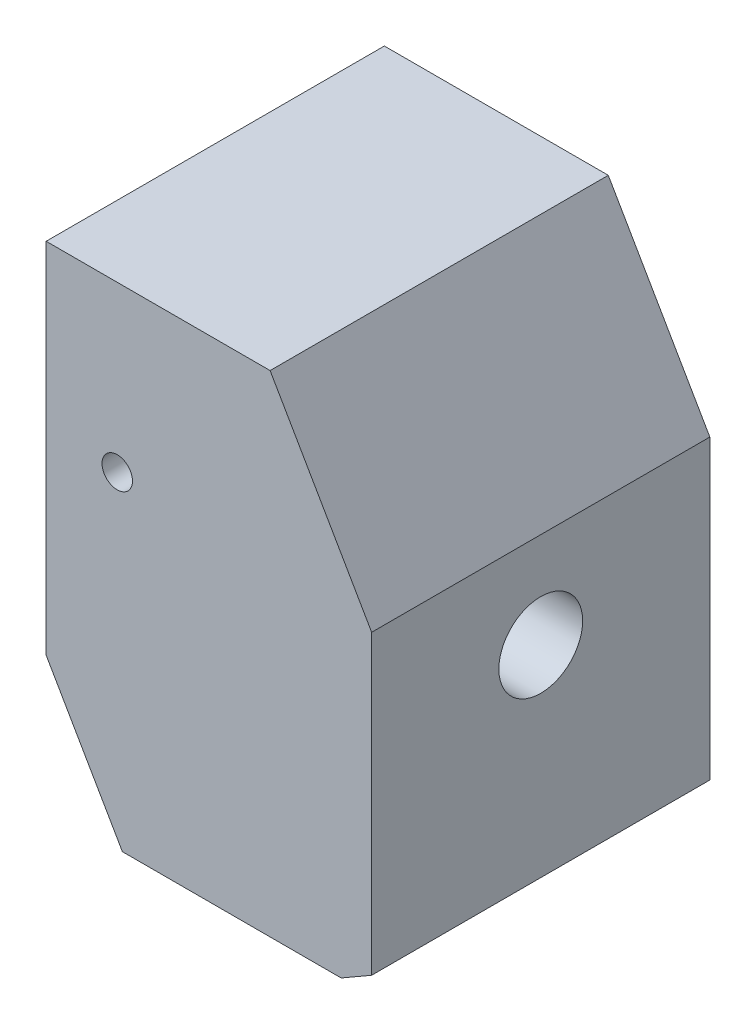
SolidWorks part; units mm, degrees
ref_plane "Front Plane" through (0, 0, 0) normal (0, 0, 1) x (1, 0, 0)
ref_plane "Top Plane" through (0, 0, 0) normal (0, 1, 0) x (1, 0, 0)
ref_plane "Right Plane" through (0, 0, 0) normal (1, 0, 0) x (0, 0, -1)
sketch "Sketch1" plane through (0, 0, 0) normal (1, 0, 0) x (0, 0, -1)
  line L1 (-16.65, 24.15) -> (16.65, 24.15)
  line L2 (-16.65, 24.15) -> (-16.65, -24.15)
  line L3 (-16.65, -24.15) -> (16.65, -24.15)
  line L4 (16.65, 24.15) -> (16.65, -24.15)
  line L5 (-16.65, 24.15) -> (16.65, -24.15) construction
  line L6 (-16.65, -24.15) -> (16.65, 24.15) construction
  point P0 (0, 0)
  dimension "D1" = 48.3
  dimension "D2" = 33.3
extrude "Boss-Extrude1" add sketch "Sketch1" along normal blind 9.55
sketch "Sketch2" plane through (0, 0, 0) normal (-1, 0, 0) x (0, 0, 1)
  line L0 (0, 24.15) -> (0, 19.15) construction
  line L3 (-16.65, 24.15) -> (16.65, 24.15) construction
  line L4 (0, 19.15) -> (0, -19.451) construction
  line L5 (0, -19.451) -> (0, -24.15) construction
  line L6 (16.65, -24.15) -> (-16.65, -24.15) construction
  line L7 (0, 19.15) -> (-5.65, 19.15)
  line L8 (-5.65, 19.15) -> (-5.65, 5.45)
  line L9 (-5.65, 5.45) -> (-11.65, -0.9874)
  line L10 (-11.65, -0.9874) -> (-11.65, -9.1)
  line L11 (-11.65, -9.1) -> (-10.5771, -10.1)
  line L12 (-10.5771, -10.1) -> (10.5771, -10.1)
  line L13 (11.65, -9.1) -> (10.5771, -10.1)
  line L14 (11.65, -0.9874) -> (11.65, -9.1)
  line L15 (5.65, 5.45) -> (11.65, -0.9874)
  line L16 (5.65, 5.45) -> (5.65, 11.45)
  line L17 (5.65, 11.45) -> (4.5, 12.6)
  line L18 (4.5, 12.6) -> (4.5, 19.15)
  line L19 (4.5, 19.15) -> (0, 19.15)
  point P16 (0, -10.1)
  dimension "D1" = 5
  dimension "D2" = 4.699
  dimension "D3" = 11.65
  dimension "D4" = 15.55
  dimension "D5" = 5.65
  dimension "D6" = 13.7
  dimension "D7" = 8.8
  dimension "D8" = 1
  dimension "D9" = 6
  dimension "D10" = 7.15
  dimension "D11" = 4.5
extrude "Cut-Extrude1" cut sketch "Sketch2" against normal blind 5
sketch "Sketch3" plane through (5, 0, 0) normal (-1, 0, 0) x (0, 0, 1)
  line L0 (-5.65, 19.15) -> (4.5, 19.15)
  line L1 (4.5, 19.15) -> (4.5, 12.6)
  line L2 (4.5, 12.6) -> (5.65, 11.45)
  line L3 (5.65, 11.45) -> (5.65, 5.45)
  line L4 (5.65, 5.45) -> (-5.65, 5.45)
  line L5 (-5.65, 5.45) -> (-5.65, 19.15)
extrude "Cut-Extrude2" cut sketch "Sketch3" against normal blind 4.5
sketch "Sketch5" plane through (9.55, 0, 0) normal (1, 0, 0) x (0, 0, -1)
  line L1 (-16.65, 24.15) -> (16.65, 24.15)
  line L2 (-16.65, 24.15) -> (-16.65, -24.15)
  line L3 (-16.65, -24.15) -> (16.65, -24.15)
  line L4 (16.65, 24.15) -> (16.65, -24.15)
  line L5 (-16.65, 24.15) -> (16.65, -24.15) construction
  line L6 (-16.65, -24.15) -> (16.65, 24.15) construction
  point P0 (0, 0)
extrude "Boss-Extrude3" add sketch "Sketch5" along normal blind 22.5
sketch "Sketch6" plane through (5, 0, 0) normal (-1, 0, 0) x (0, 0, 1)
  line L0 (0, 5.45) -> (0, -2.575) construction
  line L1 (-5.65, 5.45) -> (5.65, 5.45) construction
  line L2 (0, 1.45) -> (5.4752, 1.45) construction
  circle A0 centre (0, -2.575) radius 4.025
  dimension "D2" = 8.05
  dimension "D1" = 4
extrude "Cut-Extrude3" cut sketch "Sketch6" against normal blind 12
sketch "Sketch7" plane through (17, 0, 0) normal (-1, 0, 0) x (0, 0, 1)
  circle A0 centre (0, -2.575) radius 4.125
  dimension "D1" = 8.25
extrude "Cut-Extrude4" cut sketch "Sketch7" against normal up to surface (15.05 mm away) up to face at (32.05, 0, 0)
sketch "Sketch27" plane through (0, 0, 5.65) normal (0, 0, -1) x (-1, 0, 0)
  line L0 (-9.5, 5.45) -> (-9.5, 11.45) construction
  line L1 (-9.5, 5.45) -> (-5, 5.45) construction
  circle A0 centre (-7, 7.95) radius 1.5
  dimension "D1" = 3
  dimension "D2" = 2.5
  dimension "D3" = 2.5
extrude "Cut-Extrude6" cut sketch "Sketch27" against normal through all both and the other way through all
ref_plane "Plane1" through (18.4698, -31.9906, 0) normal (0.5, -0.866, 0) x (0, 0, -1)
sketch "Sketch28" plane through (0, 0, 0) normal (0, 0, 1) x (1, 0, 0)
  line L0 (32.05, -2.575) -> (17, -2.575) construction
  line L1 (32.05, -6.7) -> (32.05, 1.55) construction
  line L2 (17, -6.6) -> (17, 1.45) construction
  line L3 (17, -2.575) -> (17, -6.6) construction
  line L4 (17, -6.7) -> (17, 1.55) construction
  line L5 (17, -6.6) -> (13, -6.6) construction
  line L6 (13, -6.6) -> (25.3619, -28.0114)
  line L7 (3.2039, -40.8043) -> (33.7356, -23.1768) construction
  line L8 (13, -6.6) -> (10.1841, -1.7228)
  dimension "D1" = 4.025
  dimension "D2" = 4
  dimension "D3" = 60
  dimension "D4" = 180
sketch "Sketch29" plane through (0, 0, 0) normal (0, 0, 1) x (1, 0, 0)
  line L0 (32.05, -2.575) -> (17, -2.575) construction
  line L1 (32.05, -6.7) -> (32.05, 1.55) construction
  line L2 (19, -16.9923) -> (25.3619, -28.0114)
  line L3 (17, -2.575) -> (17, -6.6) construction
  line L4 (3.2039, -40.8043) -> (33.7356, -23.1768) construction
  line L5 (17, -6.6) -> (13, -6.6) construction
  line L6 (13, -6.6) -> (19, -16.9923) construction
  line L8 (13, -6.6) -> (25.3619, -28.0114) construction
  dimension "D1" = 4.025
  dimension "D2" = 4
  dimension "D3" = 12
  dimension "D4" = 60
sketch "Sketch30" plane through (18.4698, -31.9906, 0) normal (0.5, -0.866, 0) x (0, 0, -1)
  circle A0 centre (0, 7.9583) radius 3
  point P3 (0, 0)
  dimension "D1" = 6
sweep "Cut-Sweep1" cut profiles "Sketch30" path "Sketch28"
sketch "Sketch31" plane through (18.4698, -31.9906, 0) normal (0.5, -0.866, 0) x (0, 0, -1)
  circle A0 centre (0, 7.9583) radius 4
  dimension "D1" = 8
sweep "Cut-Sweep2" cut profiles "Sketch31" path "Sketch29"
chamfer "Chamfer1" distance 13 angle 30 1 edges at (0, -24.15, 0) first distance on face at (0, 2.7396, 0.75)
chamfer "Chamfer2" distance 10 angle 60 1 edges at (32.05, 24.15, 0) first distance on face at (16.025, 24.15, 0)
chamfer "Chamfer3" distance 3 angle 30 1 edges at (32.05, -24.15, 0) first distance on face at (27.7513, -24.15, 0)
